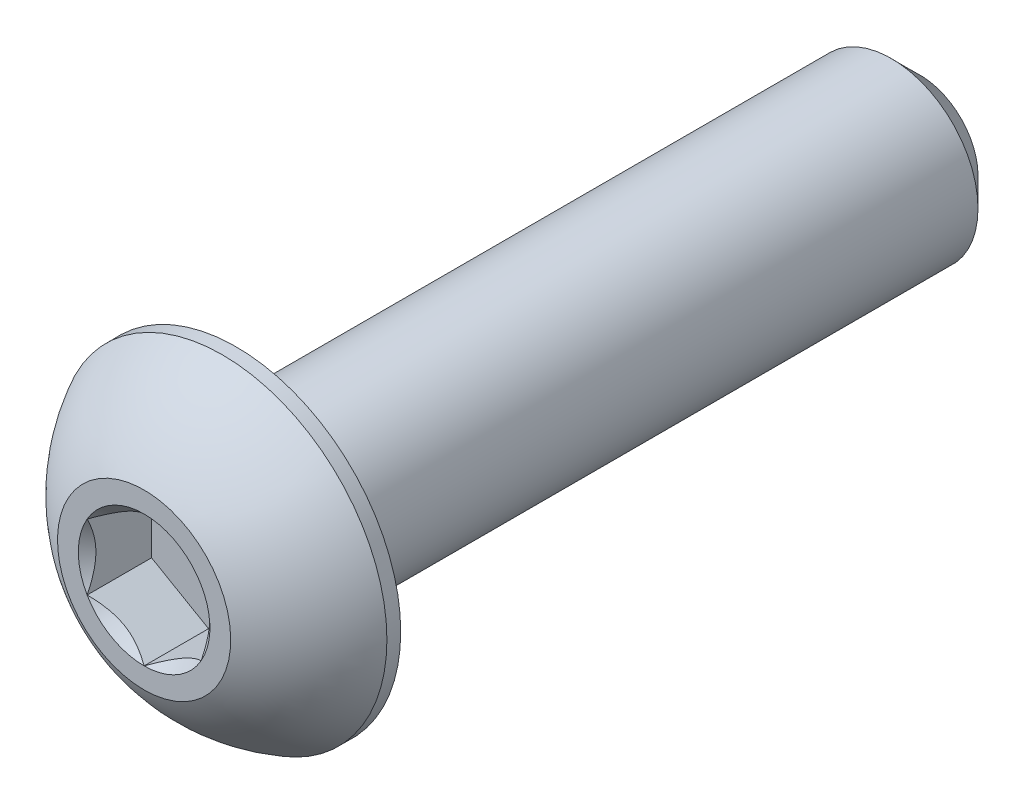
SolidWorks part; units mm, degrees
ref_plane "Front" through (0, 0, 0) normal (0, 0, 1) x (1, 0, 0)
ref_plane "Top" through (0, 0, 0) normal (0, 1, 0) x (1, 0, 0)
ref_plane "Right" through (0, 0, 0) normal (1, 0, 0) x (0, 0, -1)
sketch "Sketch1" plane through (0, 0, 0) normal (1, 0, 0) x (0, 0, -1)
  line L2 (2.5654, 2.413) -> (21.6154, 2.413)
  line L3 (21.6154, 2.413) -> (21.6154, 0)
  line L4 (21.6154, 0) -> (2.5654, 0)
  line L6 (2.1806, 4.5847) -> (2.5654, 4.5847) construction
  line L7 (21.6154, 2.413) -> (21.6154, -2.413) construction
  line L8 (0, 0) -> (2.5654, 0) construction
  line L9 (2.5654, 4.5847) -> (2.5654, -4.5847) construction
  line L11 (2.5654, 2.413) -> (2.5654, 0)
  line L13 (0, 1.5875) -> (0, -1.5875) construction
  line L14 (0, 1.5875) -> (0, 2.413) construction
  arc A3 (0, 2.413) -> (2.1806, 4.5847) centre (4.5749, 0) cw construction
  dimension "D1" = 0.3848
revolve "Revolve1" add sketch "Sketch1" angle 360 mid plane about L4
sketch "Sketch3" plane through (0, 0, -21.6154) normal (0, 0, -1) x (-1, 0, 0)
  circle A0 centre (0, 0) radius 2.413
curve "Helix/Spiral1" pitch 1.0583 height 20.1083 turns 19
sketch "Sketch2" plane through (0, 0, 0) normal (1, 0, 0) x (0, 0, -1)
  line L0 (21.6154, 2.413) -> (22.5414, 2.413)
  line L1 (22.5414, 2.413) -> (22.1446, 1.7256)
  line L2 (22.1446, 1.7256) -> (22.0123, 1.7256)
  line L3 (22.0123, 1.7256) -> (21.6154, 2.413)
  line L4 (21.8138, 2.0693) -> (22.343, 2.0693) construction
  dimension "D1" = 60
  dimension "D2" = 0.1323
  dimension "D3" = 0.5292
chamfer "Chamfer1" distance 0.7937 angle 45 1 edges at (0, 2.413, -21.6154)
sweep "Cut-Sweep1" [suppressed] cut profiles "Sketch2" path "Helix/Spiral1"
sketch "Sketch7" plane through (0, 0, 0) normal (1, 0, 0) x (0, 0, -1)
  line L6 (2.1806, 4.5847) -> (2.5654, 4.5847) construction
  line L8 (0, 0) -> (2.5654, 0) construction
  line L11 (2.5654, 4.5847) -> (2.5654, -4.5847) construction
  line L12 (2.1806, 4.5847) -> (2.5654, 4.5847)
  line L13 (0, 0) -> (2.5654, 0)
  line L14 (0, 1.5875) -> (0, -1.5875) construction
  line L15 (2.5654, 4.5847) -> (2.5654, 0)
  line L16 (0, 2.413) -> (0, 0)
  arc A2 (2.1806, 4.5847) -> (0, 2.413) centre (4.5749, 0) ccw construction
  arc A3 (2.1806, 4.5847) -> (0, 2.413) centre (4.5749, 0) ccw
revolve "Revolve2" add sketch "Sketch7" angle 360 mid plane about L13
sketch "Sketch5" plane through (0, 0, 0) normal (0, 0, 1) x (1, 0, 0)
  line L1 (1.5875, -0.9165) -> (1.5875, 0.9165)
  line L2 (1.5875, 0.9165) -> (0, 1.8331)
  line L3 (0, 1.8331) -> (-1.5875, 0.9165)
  line L4 (-1.5875, 0.9165) -> (-1.5875, -0.9165)
  line L5 (-1.5875, -0.9165) -> (0, -1.8331)
  line L6 (0, -1.8331) -> (1.5875, -0.9165)
  circle A0 centre (0, 0) radius 1.5875 construction
extrude "Cut-Extrude2" cut sketch "Sketch5" against normal blind 1.7958
sketch "Sketch6" plane through (0, 0, 0) normal (0, 0, 1) x (1, 0, 0)
  circle A0 centre (0, 0) radius 1.8331
extrude "Cut-Extrude3" cut sketch "Sketch6" against normal blind 1.7958 draft 45
sketch "Sketch9" [suppressed] plane through (0, 0, -2.5654) normal (0, 0, 1) x (1, 0, 0)
  circle A2 centre (0, 0) radius 2.413
extrude "Boss-Extrude2" [suppressed] add sketch "Sketch9" against normal offset from surface (3.175 mm away) 28.575
sketch "Sketch10" plane through (0, 0, 0) normal (1, 0, 0) x (0, 0, -1)
  line L0 (21.6154, 2.413) -> (21.6154, -2.413) construction
  point P0 (20.0279, -2.413)
  dimension "D1" = 1.5875
equation "\"D3@Helix/Spiral1\" = \"Lg@Sketch1\" + \"D4@Helix/Spiral1\""
equation "\"D2@Sketch2\" = \"D4@Helix/Spiral1\" * .125"
equation "\"D3@Sketch2\" = \"D4@Helix/Spiral1\" * .5"
equation "\"D1@Chamfer1\" = \"D4@Helix/Spiral1\" * .75"
equation "\"D1@Cut-Extrude2\" = \"Head Ht@Sketch1\" * .7"
equation "\"D1@Sketch1\" = \"Head Ht@Sketch1\" * .15"
equation "\"D1@Sketch10\" = \"D4@Helix/Spiral1\" * 1.5"
equation "\"D1@Cut-Extrude3\" = \"D1@Cut-Extrude2\""
